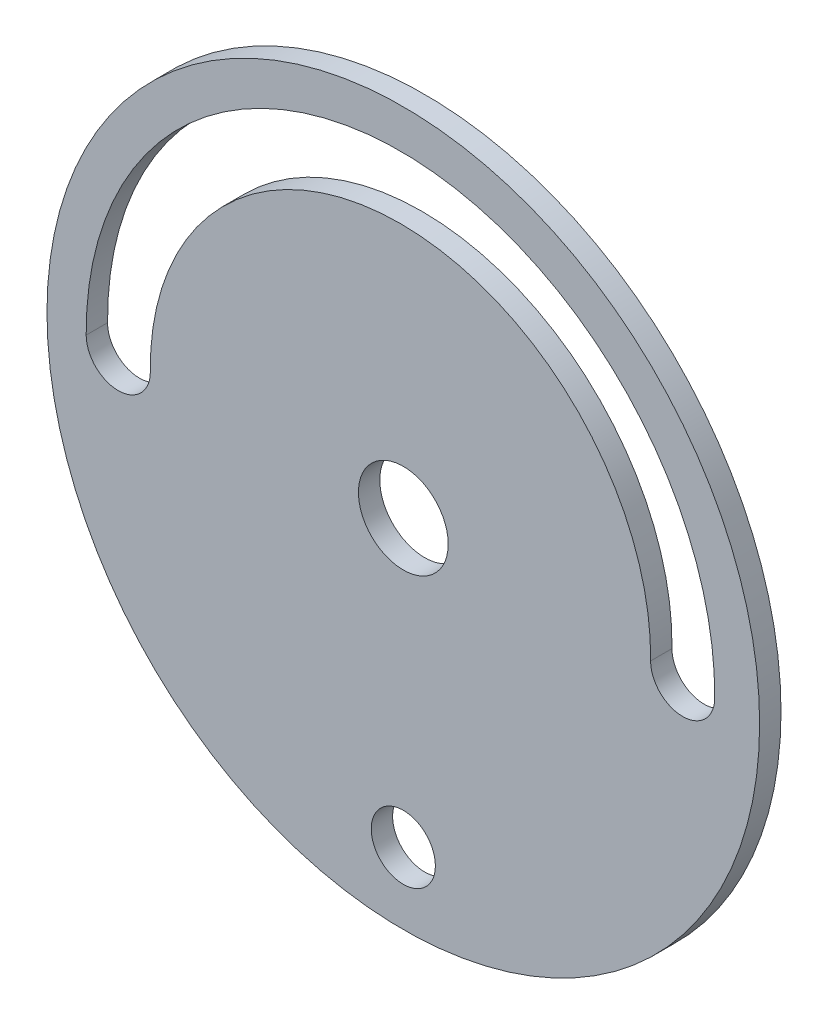
SolidWorks part; units mm, degrees
ref_plane "Front Plane" through (0, 0, 0) normal (0, 0, 1) x (1, 0, 0)
ref_plane "Top Plane" through (0, 0, 0) normal (0, 1, 0) x (1, 0, 0)
ref_plane "Right Plane" through (0, 0, 0) normal (1, 0, 0) x (0, 0, -1)
sketch "Sketch1" plane through (0, 0, 0) normal (0, 0, 1) x (1, 0, 0)
  line L0 (-27.0565, 7.3948) -> (22.9435, 7.3948) construction
  line L1 (-2.2565, 25.1948) -> (-2.2565, 29.5948) construction
  circle A0 centre (-2.0565, 7.3948) radius 25
  circle A2 centre (-2.0565, -12.6052) radius 2.25
  arc A3 (19.7935, 7.3948) -> (-24.3065, 7.3948) centre (-2.2565, 7.5443) ccw
  arc A4 (15.2935, 7.3948) -> (-19.8065, 7.3948) centre (-2.2565, 7.6431) ccw
  arc A5 (19.7935, 7.3948) -> (15.2935, 7.3948) centre (17.5435, 7.3948) cw
  arc A6 (-24.3065, 7.3948) -> (-19.8065, 7.3948) centre (-22.0565, 7.3948) ccw
  circle A7 centre (-2.0565, 7.3948) radius 3.15
  point P2 (-2.2565, 27.3948)
  dimension "D1" = 4.5
  dimension "D2" = 50
  dimension "D4" = 6.3
  dimension "D3" = 20
  dimension "D5" = 4.4
  dimension "D6" = 20
extrude "Boss-Extrude1" add sketch "Sketch1" along normal blind 1.5
